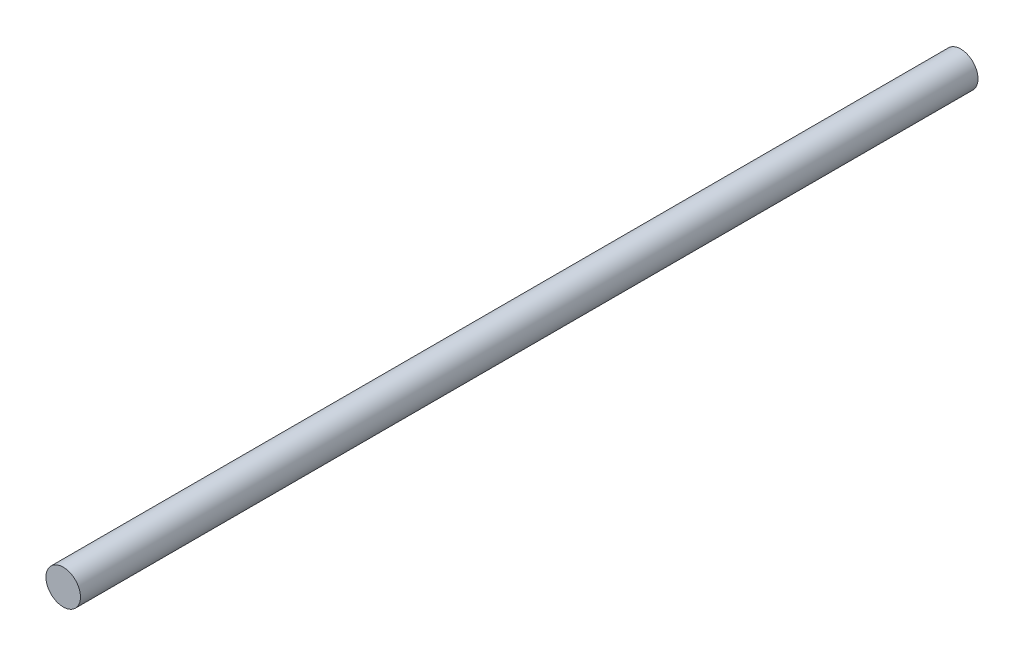
SolidWorks part; units mm, degrees
material "Pine"
ref_plane "Front Plane" through (0, 0, 0) normal (0, 0, 1) x (1, 0, 0)
ref_plane "Top Plane" through (0, 0, 0) normal (0, 1, 0) x (1, 0, 0)
ref_plane "Right Plane" through (0, 0, 0) normal (1, 0, 0) x (0, 0, -1)
sketch "Sketch1" plane through (0, 0, 0) normal (0, 0, 1) x (1, 0, 0)
  circle A0 centre (0, 0) radius 5
  dimension "D1" = 10
extrude "Boss-Extrude1" add sketch "Sketch1" along normal blind 130 and the other way blind 130
